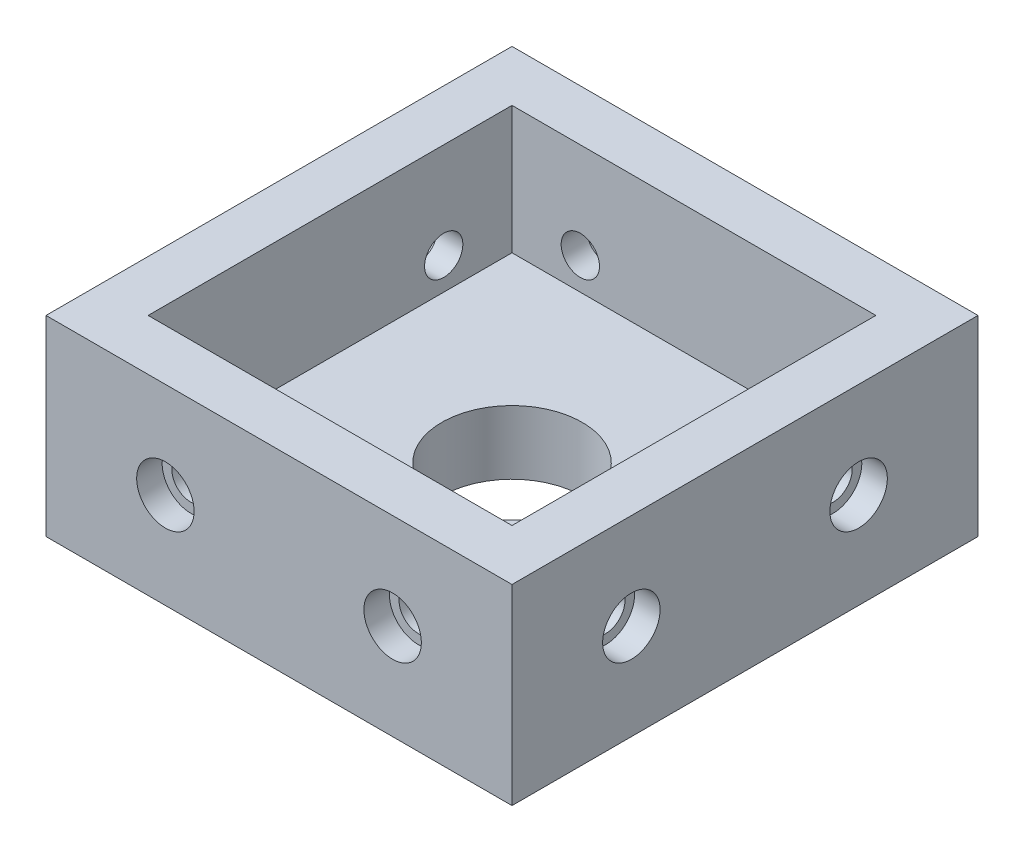
SolidWorks part; units mm, degrees
note: The reader was unsure of these and kept them because the rebuilt part matched: shared geometry of "草图1<18>", "草图2<3>", "草图2<4>", "草图3<4>", "草图3<5>", "草图4<3>", "草图4<4>", "草图4<5>", "草图4<6>", "草图4<7>".
ref_plane "前视基准面" through (0, 0, 0) normal (0, 0, 1) x (1, 0, 0)
ref_plane "上视基准面" through (0, 0, 0) normal (0, 1, 0) x (1, 0, 0)
ref_plane "右视基准面" through (0, 0, 0) normal (1, 0, 0) x (0, 0, -1)
other "Configuration Table"
sketch "草图1" plane through (0, 0, 0) normal (0, 1, 0) x (1, 0, 0)
  line L1 (0, -14.25) -> (28.5, -14.25)
  line L2 (0, -14.25) -> (0, 14.25)
  line L3 (0, 14.25) -> (28.5, 14.25)
  line L4 (28.5, -14.25) -> (28.5, 14.25)
  line L5 (-4, 18.25) -> (32.5, 18.25)
  line L6 (-4, 18.25) -> (-4, -18.25)
  line L7 (-4, -18.25) -> (32.5, -18.25)
  line L8 (32.5, 18.25) -> (32.5, -18.25)
  circle A0 centre (14.25, 0) radius 5.5
  point P0 (0, 0)
  point P10 (14.25, 14.25)
  dimension "D1" = 28.5
  dimension "D2" = 28.5
  dimension "D3" = 11
  dimension "D4" = 4
  dimension "D5" = 4
  dimension "D6" = 4
  dimension "D7" = 4
extrude "凸台-拉伸1" add sketch "草图1" along normal blind 5 contours A0 | L5 L8 L7 L6
extrude "凸台-拉伸2" add sketch "草图1<18>" along normal blind 10 from surface at 5 contours L8 L7 L6 L5 | L3 L4 L1 L2 starting at face at (14.25, 5, 0)
sketch "草图1<18>" plane through (0, 0, 0) normal (0, 1, 0) x (1, 0, 0) same geometry as "草图1"
sketch "草图2" plane through (0, 0, -18.25) normal (0, 0, -1) x (-1, 0, 0)
  circle A0 centre (-23.15, 7.5) radius 1.5
  circle A1 centre (-5.35, 7.5) radius 1.5
  circle A2 centre (-23.15, 7.5) radius 2.25
  circle A3 centre (-5.35, 7.5) radius 2.25
  dimension "D1" = 4.5
  dimension "D2" = 3
sketch "草图3" plane through (-4, 0, 0) normal (-1, 0, 0) x (0, 0, 1)
  circle A0 centre (-8.9, 7.5) radius 2.25
  circle A1 centre (-8.9, 7.5) radius 1.5
  circle A2 centre (8.9, 7.5) radius 2.25
  circle A3 centre (8.9, 7.5) radius 1.5
  dimension "D1" = 4.5
  dimension "D2" = 3
extrude "切除-拉伸1" cut sketch "草图2" against normal through all contours A0 | A1
extrude "切除-拉伸2" cut sketch "草图2<3>" against normal offset from surface (2 mm away) 2 contours A2 | A3 up to face at (24.65, 7.5, -14.25)
sketch "草图2<3>" plane through (0, 0, -18.25) normal (0, 0, -1) x (-1, 0, 0) same geometry as "草图2"
extrude "切除-拉伸3" cut sketch "草图2<4>" along normal offset from surface (2 mm away) 2 from surface at -36.5 up to face at (24.65, 7.5, 14.25) starting at face at (21.65, 7.5, 18.25)
sketch "草图2<4>" plane through (0, 0, -18.25) normal (0, 0, -1) x (-1, 0, 0) same geometry as "草图2"
extrude "切除-拉伸4" cut sketch "草图3" against normal through all contours A1 | A3
extrude "切除-拉伸8" cut sketch "草图3<4>" against normal offset from surface (2 mm away) 2 contours A0 | A2 up to face at (0, 7.5, -10.4)
sketch "草图3<4>" plane through (-4, 0, 0) normal (-1, 0, 0) x (0, 0, 1) same geometry as "草图3"
extrude "切除-拉伸9" cut sketch "草图3<5>" along normal offset from surface (2 mm away) 2 from surface at -36.5 contours A0 | A2 up to face at (28.5, 7.5, -10.4) starting at face at (32.5, 7.5, -7.4)
sketch "草图3<5>" plane through (-4, 0, 0) normal (-1, 0, 0) x (0, 0, 1) same geometry as "草图3"
sketch "草图4" plane through (0, 0, 0) normal (0, -1, 0) x (1, 0, 0)
  line L0 (-4, -18.25) -> (32.5, -18.25) construction
  line L1 (-4, 18.25) -> (39.75, 18.25)
  line L2 (-4, 18.25) -> (-4, -18.25)
  line L3 (-4, -18.25) -> (39.75, -18.25)
  line L4 (39.75, 18.25) -> (39.75, -18.25)
  line L6 (7.25, 11) -> (39.75, 11)
  line L7 (7.25, 11) -> (7.25, -11)
  line L8 (7.25, -11) -> (39.75, -11)
  line L9 (39.75, 11) -> (39.75, -11)
  line L10 (2.75, 15.5) -> (39.75, 15.5)
  line L11 (2.75, 15.5) -> (2.75, -15.5)
  line L12 (2.75, -15.5) -> (39.75, -15.5)
  line L13 (39.75, 15.5) -> (39.75, -15.5)
  circle A0 centre (27.25, 0) radius 1
  circle A4 centre (27.25, 0) radius 10
  circle A5 centre (33.75, 0) radius 5
  circle A9 centre (14.25, 0) radius 5.5
  circle A10 centre (14.25, 0) radius 5.5 construction
  circle A11 centre (23.5, 13.25) radius 0.75
  circle A12 centre (23.5, 13.25) radius 1.5
  circle A13 centre (5, 0) radius 0.75
  circle A14 centre (5, 0) radius 1.5
  circle A15 centre (23.5, -13.25) radius 0.75
  circle A16 centre (23.5, -13.25) radius 1.5
  point P14 (7.25, 0)
  point P34 (23.5, 11)
  point P38 (2.75, 0)
  dimension "D1" = 2
  dimension "D2" = 20
  dimension "D3" = 10
  dimension "D4" = 6
  dimension "D10" = 3
  dimension "D11" = 1.5
  dimension "D5" = 11
  dimension "D6" = 7
  dimension "D7" = 4.5
  dimension "D8" = 4.5
  dimension "D9" = 4.5
  dimension "D12" = 2.25
  dimension "D13" = 2.25
  dimension "D14" = 2.25
extrude "凸台-拉伸3" add sketch "草图4" along normal blind 6 contours L8 L9 L6 L7 | A9
extrude "凸台-拉伸4" add sketch "草图4<3>" along normal blind 8 from surface at 14 contours L7 L8 L9 L6 | A9 | A4 | A5
sketch "草图4<3>" plane through (0, 0, 0) normal (0, -1, 0) x (1, 0, 0) same geometry as "草图4"
extrude "切除-拉伸10" cut sketch "草图4<4>" against normal blind 5 from surface at 6 contours A0 starting at face at (28.1513, -6, 0)
sketch "草图4<4>" plane through (0, 0, 0) normal (0, -1, 0) x (1, 0, 0) same geometry as "草图4"
extrude "凸台-拉伸5" add sketch "草图4<5>" along normal blind 2 contours L11 L12 L13 L10 | L7 L8 L9 L6
sketch "草图4<5>" plane through (0, 0, 0) normal (0, -1, 0) x (1, 0, 0) same geometry as "草图4"
extrude "切除-拉伸11" cut sketch "草图4<6>" against normal blind 4 from surface at 0 contours A11 | A13 | A15 starting at face at (15.9375, 0, 0)
sketch "草图4<6>" plane through (0, 0, 0) normal (0, -1, 0) x (1, 0, 0) same geometry as "草图4"
extrude "切除-拉伸12" cut sketch "草图4<7>" along normal up to next contours A14 | A12 | A16
sketch "草图4<7>" plane through (0, 0, 0) normal (0, -1, 0) x (1, 0, 0) same geometry as "草图4"
sketch "草图5" plane through (0, 0, 0) normal (0, -1, 0) x (1, 0, 0)
  line L1 (-100, -50) -> (100, -50)
  line L2 (-100, -50) -> (-100, 50)
  line L3 (-100, 50) -> (100, 50)
  line L4 (100, -50) -> (100, 50)
  line L5 (-100, -50) -> (100, 50) construction
  line L6 (-100, 50) -> (100, -50) construction
  point P0 (0, 0)
  dimension "D1" = 100
  dimension "D2" = 200
extrude "切除-拉伸13" cut sketch "草图5" along normal through all
